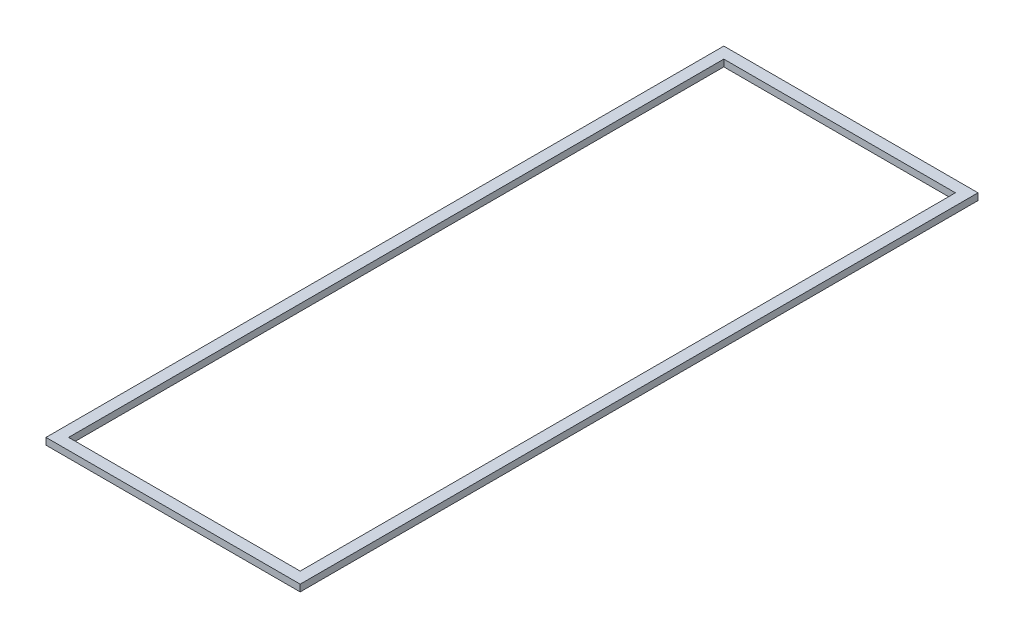
SolidWorks part; units mm, degrees
ref_plane "Спереди" through (0, 0, 0) normal (0, 0, 1) x (1, 0, 0)
ref_plane "Сверху" through (0, 0, 0) normal (0, 1, 0) x (1, 0, 0)
ref_plane "Справа" through (0, 0, 0) normal (1, 0, 0) x (0, 0, -1)
sketch "Эскиз1" plane through (0, 0, 0) normal (0, 1, 0) x (1, 0, 0)
  line L1 (0, 0) -> (450, 0)
  line L2 (0, 0) -> (0, 1200)
  line L3 (0, 1200) -> (450, 1200)
  line L4 (450, 0) -> (450, 1200)
extrude "Вытянуть-Тонкостенный1" add sketch "Эскиз1" along normal blind 12 thin thin type one direction reverse wall 20
